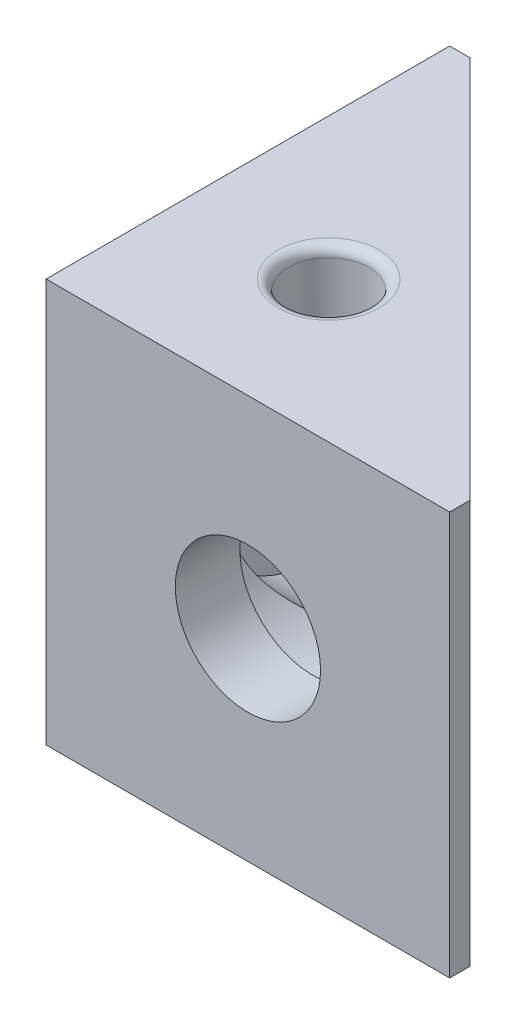
SolidWorks part; units mm, degrees
ref_plane "Front Plane" through (0, 0, 0) normal (0, 0, 1) x (1, 0, 0)
ref_plane "Top Plane" through (0, 0, 0) normal (0, 1, 0) x (1, 0, 0)
ref_plane "Right Plane" through (0, 0, 0) normal (1, 0, 0) x (0, 0, -1)
sketch "Sketch2" plane through (0, 0, 0) normal (0, 1, 0) x (1, 0, 0)
  line L0 (0, 0) -> (0, 20)
  line L2 (20, 0) -> (0, 0)
  line L3 (0, 20) -> (1, 20)
  line L4 (20, 0) -> (20, 1)
  line L5 (1, 20) -> (20, 1)
  dimension "D1" = 20
  dimension "D2" = 1
extrude "Boss-Extrude1" add sketch "Sketch2" along normal mid plane 20
sketch "Sketch3" plane through (0, 0, 0) normal (0, 0, 1) x (1, 0, 0)
  line L0 (0, 10) -> (20, -10) construction
  line L1 (20, 10) -> (0, 0) construction
  circle A0 centre (10, 0) radius 3.6
  circle A1 centre (10, 0) radius 5.5
  dimension "D1" = 7.2
  dimension "D2" = 11
extrude "Cut-Extrude1" cut sketch "Sketch3" against normal up to surface (7.4 mm away) contours A0 region at (10, 0, 0) up to face at (10.5, 0, -10.5)
extrude "Cut-Extrude3" cut sketch "Sketch3<4>" against normal up to surface (4.2 mm away) from offset 3.2 up to face at (13.6, 0, -7.4) offset against normal yes
sketch "Sketch3<4>" plane through (0, 0, 0) normal (0, 0, 1) x (1, 0, 0) same geometry as "Sketch3"
sketch "Sketch4" plane through (0, 0, 0) normal (-1, 0, 0) x (0, 0, 1)
  line L0 (-20, 10) -> (0, -10) construction
  line L1 (0, 10) -> (-20, -10) construction
  circle A0 centre (-10, 0) radius 3.6
  circle A1 centre (-10, 0) radius 5.5
  point P11 (-10, 0)
  dimension "D1" = 7.2
  dimension "D2" = 11
extrude "Cut-Extrude2" cut sketch "Sketch4" against normal up to surface (14.6 mm away) contours A0 region at (0, 0, -10) up to face at (15.5, 0, -5.5)
extrude "Cut-Extrude4" cut sketch "Sketch4<3>" against normal up to surface (11.4 mm away) from offset 3.2 up to face at (15.5, 0, -5.5) offset against normal yes
sketch "Sketch4<3>" plane through (0, 0, 0) normal (-1, 0, 0) x (0, 0, 1) same geometry as "Sketch4"
sketch "Sketch5" plane through (0, 10, 0) normal (0, 1, 0) x (1, 0, 0)
  line L0 (0, 0) -> (10.5, 10.5) construction
  line L1 (20, 1) -> (1, 20) construction
  line L2 (0, 0) -> (20, 0) construction
  circle A0 centre (7, 7) radius 2
  dimension "D1" = 4
  dimension "D2" = 7
extrude "Cut-Extrude5" cut sketch "Sketch5" against normal blind 4.5
fillet "Fillet1" radius 0.5 1 edges at (7, 10, -5)
